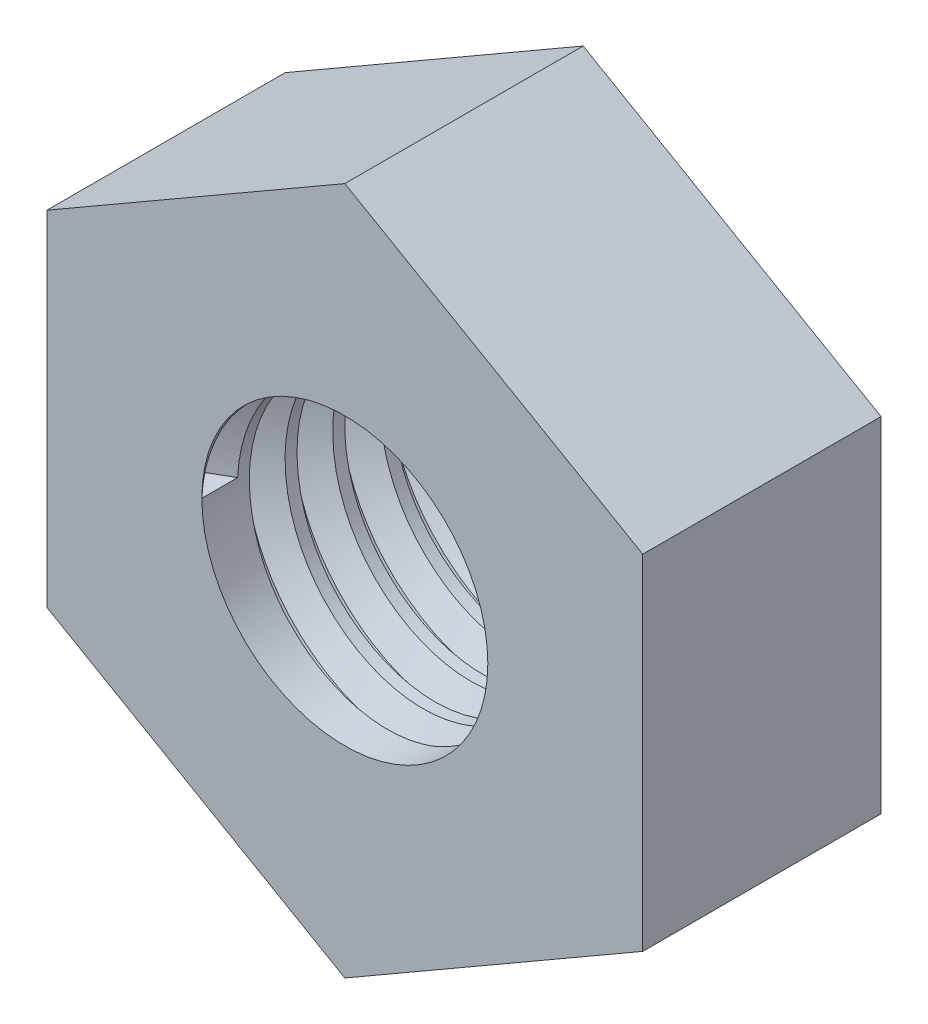
SolidWorks part; units mm, degrees
ref_plane "Front Plane" through (0, 0, 0) normal (0, 0, 1) x (1, 0, 0)
ref_plane "Top Plane" through (0, 0, 0) normal (0, 1, 0) x (1, 0, 0)
ref_plane "Right Plane" through (0, 0, 0) normal (1, 0, 0) x (0, 0, -1)
sketch "Sketch1" plane through (0, 0, 0) normal (0, 0, 1) x (1, 0, 0)
  line L1 (6.25, -3.6084) -> (6.25, 3.6084)
  line L2 (6.25, 3.6084) -> (0, 7.2169)
  line L3 (0, 7.2169) -> (-6.25, 3.6084)
  line L4 (-6.25, 3.6084) -> (-6.25, -3.6084)
  line L5 (-6.25, -3.6084) -> (0, -7.2169)
  line L6 (0, -7.2169) -> (6.25, -3.6084)
  circle A0 centre (0, 0) radius 3
  circle A1 centre (0, 0) radius 6.25 construction
  dimension "D1" = 6
  dimension "D2" = 12.5
extrude "Boss-Extrude1" add sketch "Sketch1" along normal blind 5
thread "Thread1" pitch 1 method cut profile "Thread Profile1" start angle 0, offset 0, length 0, pitch 1, diameter 6
ref_plane "Plane1" through (-3, 0, 5) normal (0, -1, 0) x (-1, 0, 0)
sketch "Thread Profile1" plane through (-3, 0, 5) normal (0, -1, 0) x (-1, 0, 0)
  line L0 (0, 0) -> (0, 1) construction
  line L1 (0, 0) -> (0.5413, 0.3125)
  line L2 (0.5413, 0.3125) -> (0.5413, 0.4375)
  line L3 (0.5413, 0.4375) -> (0, 0.75)
  line L4 (0.5413, 0.375) -> (0, 0.375) construction
  line L11 (0, 0) -> (0, 0.75)
  point P2 (0, 0)
  dimension "Pitch" = 1
  dimension "Profile_Angle" = 60
  dimension "Profile_Land" = 0.125
  dimension "Profile_Height" = 0.5413
